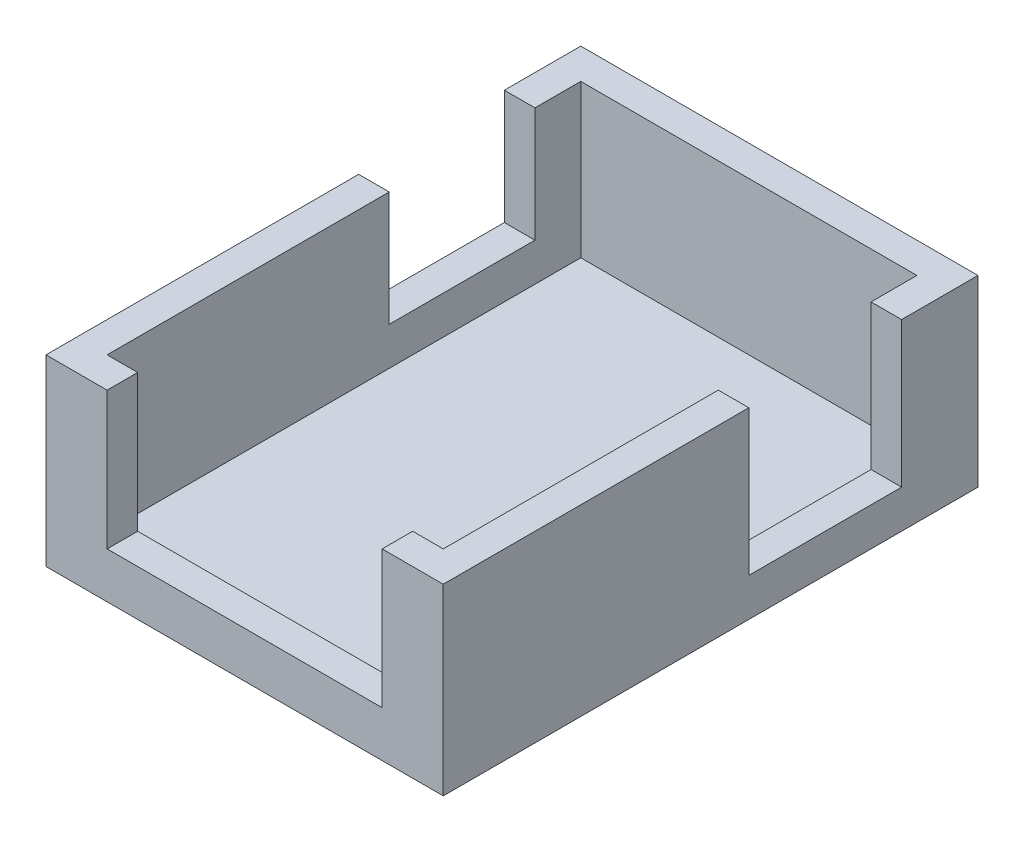
SolidWorks part; units mm, degrees
ref_plane "Płaszczyzna przednia" through (0, 0, 0) normal (0, 0, 1) x (1, 0, 0)
ref_plane "Płaszczyzna górna" through (0, 0, 0) normal (0, 1, 0) x (1, 0, 0)
ref_plane "Płaszczyzna prawa" through (0, 0, 0) normal (1, 0, 0) x (0, 0, -1)
sketch "Szkic1" plane through (0, 0, 0) normal (0, 1, 0) x (1, 0, 0)
  line L1 (-13, -17.5) -> (13, -17.5)
  line L2 (-13, -17.5) -> (-13, 17.5)
  line L3 (-13, 17.5) -> (13, 17.5)
  line L4 (13, -17.5) -> (13, 17.5)
  line L5 (-13, -17.5) -> (13, 17.5) construction
  line L6 (-13, 17.5) -> (13, -17.5) construction
  point P0 (0, 0)
  dimension "D1" = 26
  dimension "D2" = 35
extrude "Dodanie-wyciągnięcie1" add sketch "Szkic1" along normal blind 2
sketch "Szkic2" plane through (0, 2, 0) normal (0, 1, 0) x (1, 0, 0)
  line L0 (-13, 17.5) -> (13, 17.5)
  line L1 (13, 17.5) -> (13, -17.5)
  line L2 (13, -17.5) -> (-13, -17.5)
  line L3 (-13, -17.5) -> (-13, 17.5)
  line L5 (-11, -15.5) -> (11, -15.5)
  line L6 (-11, -15.5) -> (-11, 15.5)
  line L7 (-11, 15.5) -> (11, 15.5)
  line L8 (11, -15.5) -> (11, 15.5)
  line L9 (-11, -15.5) -> (11, 15.5) construction
  line L10 (-11, 15.5) -> (11, -15.5) construction
  point P4 (0, 0)
  dimension "D1" = 2
  dimension "D2" = 2
  dimension "D3" = 2
  dimension "D4" = 2
extrude "Dodanie-wyciągnięcie2" add sketch "Szkic2" along normal blind 10
sketch "Szkic3" plane through (13, 0, 0) normal (1, 0, 0) x (0, 0, -1)
  line L0 (17.5, 0) -> (17.5, 2.5) construction
  line L1 (17.5, 12) -> (17.5, 0) construction
  line L2 (17.5, 2.5) -> (12.5, 2.5) construction
  line L3 (12.5, 2.5) -> (2.5, 2.5)
  line L4 (2.5, 2.5) -> (2.5, 12)
  line L5 (-17.5, 12) -> (17.5, 12) construction
  line L6 (2.5, 12) -> (12.5, 12)
  line L7 (12.5, 12) -> (12.5, 2.5)
  dimension "D1" = 5
  dimension "D2" = 10
  dimension "D3" = 2.5
extrude "Wytnij-wyciągnięcie1" cut sketch "Szkic3" against normal up to surface (2 mm away) contours L3 L4 L6 L7 up to face at (11, 7, 0)
sketch "Szkic4" plane through (0, 0, 17.5) normal (0, 0, 1) x (1, 0, 0)
  line L0 (13, 0) -> (13, 3) construction
  line L1 (-13, 0) -> (13, 0) construction
  line L2 (13, 12) -> (13, 0) construction
  line L3 (13, 3) -> (9, 3) construction
  line L4 (9, 3) -> (9, 12)
  line L5 (-13, 12) -> (13, 12) construction
  line L6 (9, 12) -> (-9, 12)
  line L7 (-9, 12) -> (-9, 3)
  line L8 (-9, 3) -> (9, 3)
  line L9 (-13, 12) -> (-13, 0) construction
  dimension "D1" = 4
  dimension "D2" = 4
  dimension "D3" = 3
extrude "Wytnij-wyciągnięcie2" cut sketch "Szkic4" against normal up to surface (2 mm away) up to face at (0, 7, 15.5)
sketch "Szkic5" plane through (-13, 0, 0) normal (-1, 0, 0) x (0, 0, 1)
  line L0 (-17.5, 0) -> (-17.5, 4.5) construction
  line L1 (-17.5, 0) -> (17.5, 0) construction
  line L2 (-17.5, 12) -> (-17.5, 0) construction
  line L3 (-17.5, 4.5) -> (-12.5, 4.5) construction
  line L4 (-12.5, 4.5) -> (-12.5, 12)
  line L5 (-12.5, 12) -> (-2.9645, 12)
  line L6 (-2.9645, 12) -> (-2.9645, 4.5)
  line L7 (-2.9645, 4.5) -> (-12.5, 4.5)
  line L8 (-17.5, 12) -> (17.5, 12) construction
  dimension "D1" = 5
  dimension "D2" = 4.5
extrude "Wytnij-wyciągnięcie3" cut sketch "Szkic5" against normal up to surface (2 mm away) up to face at (-11, 7, 0)
